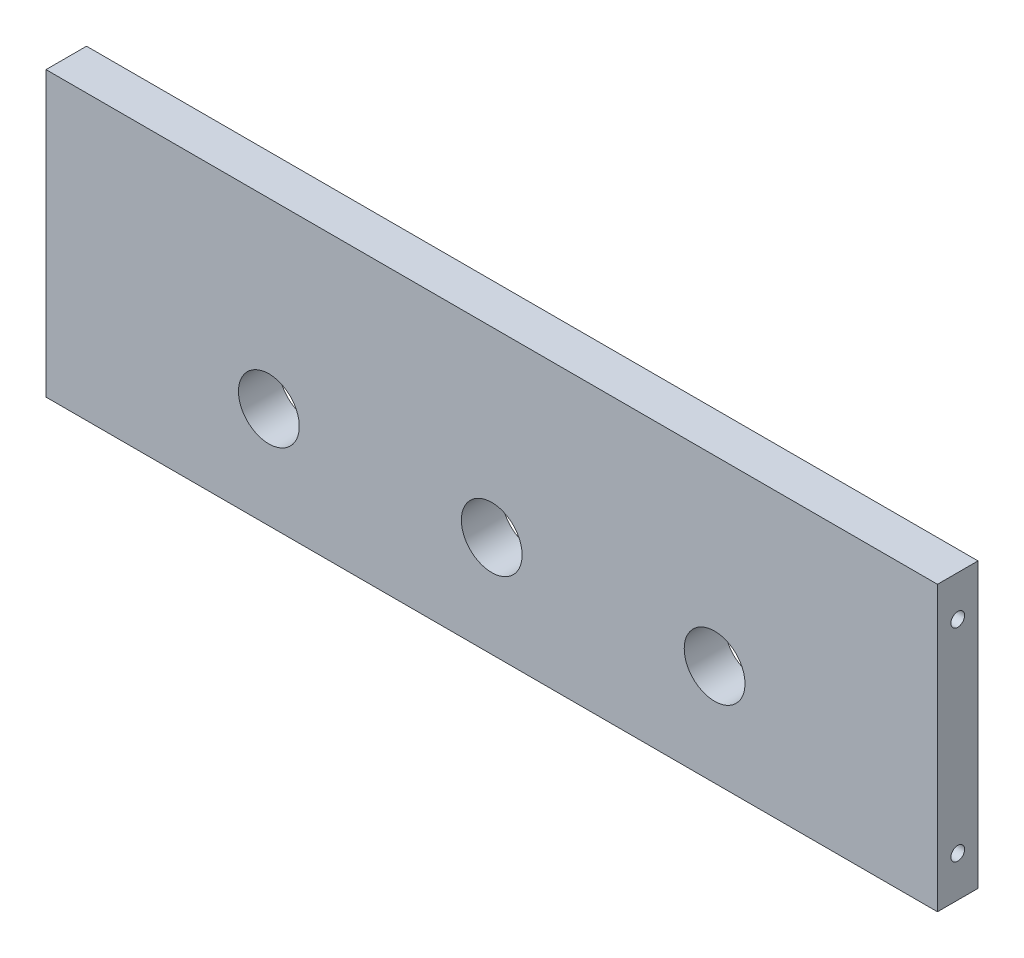
SolidWorks part; units mm, degrees
ref_plane "Front Plane" through (0, 0, 0) normal (0, 0, 1) x (1, 0, 0)
ref_plane "Top Plane" through (0, 0, 0) normal (0, 1, 0) x (1, 0, 0)
ref_plane "Right Plane" through (0, 0, 0) normal (1, 0, 0) x (0, 0, -1)
sketch "Sketch1" plane through (0, 0, 0) normal (0, 0, 1) x (1, 0, 0)
  line L1 (0, 0) -> (279.4, 0)
  line L2 (0, 0) -> (0, 88.9)
  line L3 (0, 88.9) -> (279.4, 88.9)
  line L4 (279.4, 0) -> (279.4, 88.9)
  dimension "D1" = 88.9
  dimension "D2" = 279.4
extrude "Boss-Extrude1" add sketch "Sketch1" along normal blind 12.7
sketch "Sketch2" plane through (279.4, 0, 0) normal (1, 0, 0) x (0, 0, -1)
  line L0 (-12.7, 0) -> (-12.7, 88.9) construction
  line L2 (-12.7, 0) -> (0, 0) construction
  line L3 (-12.7, 88.9) -> (0, 88.9) construction
  circle A0 centre (-6.35, 76.2) radius 2.1463
  circle A1 centre (-6.35, 12.7) radius 2.1463
  point P8 (-6.9476, 0)
  dimension "D5" = 4.2926
  dimension "D6" = 4.2926
  dimension "D1" = 6.35
  dimension "D2" = 6.35
  dimension "D3" = 12.7
  dimension "D4" = 12.7
extrude "Cut-Extrude1" cut sketch "Sketch2" against normal blind 38.1
sketch "Sketch3" plane through (0, 0, 0) normal (-1, 0, 0) x (0, 0, 1)
  line L0 (0, 88.9) -> (0, 0) construction
  line L1 (12.7, 88.9) -> (0, 88.9) construction
  line L2 (12.7, 0) -> (0, 0) construction
  circle A0 centre (6.35, 76.2) radius 2.1463
  circle A1 centre (6.35, 12.7) radius 2.1463
  dimension "D5" = 4.2926
  dimension "D6" = 4.2926
  dimension "D1" = 6.35
  dimension "D2" = 6.35
  dimension "D3" = 12.7
  dimension "D4" = 12.7
extrude "Cut-Extrude2" cut sketch "Sketch3" against normal blind 38.1
sketch "Sketch4" plane through (0, 0, 0) normal (0, 0, -1) x (-1, 0, 0)
  line L0 (0, 0) -> (-279.4, 0) construction
  line L1 (0, 88.9) -> (0, 0) construction
  line L2 (-279.4, 0) -> (-279.4, 88.9) construction
  circle A0 centre (-209.55, 31.75) radius 9.525
  circle A1 centre (-139.7, 31.75) radius 9.525
  circle A2 centre (-69.85, 31.75) radius 9.525
  dimension "D7" = 19.05
  dimension "D8" = 19.05
  dimension "D9" = 19.05
  dimension "D1" = 31.75
  dimension "D2" = 31.75
  dimension "D3" = 31.75
  dimension "D4" = 139.7
  dimension "D5" = 69.85
  dimension "D6" = 69.85
extrude "Cut-Extrude3" cut sketch "Sketch4" against normal through all
